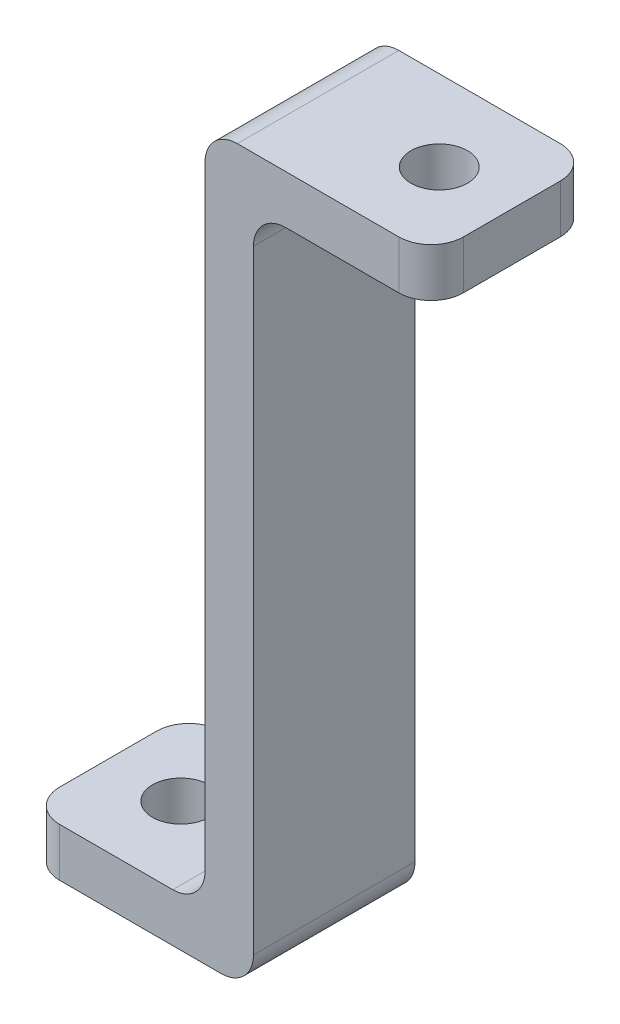
SolidWorks part; units mm, degrees
ref_plane "Front Plane" through (0, 0, 0) normal (0, 0, 1) x (1, 0, 0)
ref_plane "Top Plane" through (0, 0, 0) normal (0, 1, 0) x (1, 0, 0)
ref_plane "Right Plane" through (0, 0, 0) normal (1, 0, 0) x (0, 0, -1)
sketch "Sketch1" plane through (0, 0, 0) normal (0, 0, 1) x (1, 0, 0)
  line L0 (0, 0) -> (14, 0)
  line L1 (14, 0) -> (14, 42)
  line L2 (14, 42) -> (25, 42)
  line L3 (25, 42) -> (25, 45)
  line L4 (25, 45) -> (11, 45)
  line L5 (11, 45) -> (11, 3)
  line L6 (11, 3) -> (0, 3)
  line L7 (0, 3) -> (0, 0)
  dimension "D1" = 3
  dimension "D2" = 3
  dimension "D3" = 11
  dimension "D4" = 3
  dimension "D5" = 11
  dimension "D6" = 42
extrude "Boss-Extrude1" add sketch "Sketch1" against normal blind 10
fillet "Fillet1" radius 2 4 edges at (14, 0, -5) (11, 45, -5) (11, 3, -5) (14, 42, -5)
hole_wizard "Ø3.0mm Dowel Hole1" positions "3DSketch1" profile "Sketch2" hole size "Ø3.0" standard "ANSI Metric" end condition through all
sketch3d "3DSketch1"
  line L0 (0, 0, -5) -> (12, 0, -5) construction
  line L1 (0, 0, -10) -> (0, 0, 0) construction
  line L2 (12, 0, -10) -> (12, 0, 0) construction
  line L4 (4.5, 0, -5) -> (4.5, 0, -10) construction
  line L6 (0, 0, -10) -> (12, 0, -10) construction
  point P0 (4.5, 0, -5)
  dimension "D1" = 4.5
sketch "Sketch2" plane through (4.5, 0, -5) normal (1, 0, 0) x (0, 0, -1)
  line L0 (0, 0) -> (0, 45)
  line L1 (0, 45) -> (1.75, 45)
  line L2 (1.75, 45) -> (1.75, 0)
  line L5 (1.75, 0) -> (0, 0)
  line L11 (0, -6.35) -> (0, 107.95) construction
  dimension "Thru Hole Dia." = 3.5
  dimension "Thru Hole Depth" = 45
hole_wizard "Ø3.0mm Dowel Hole2" positions "Sketch3" profile "Sketch4" hole size "Ø3.0" standard "ANSI Metric" end condition through all
sketch "Sketch3" plane through (0, 45, 0) normal (0, 1, 0) x (1, 0, 0)
  line L0 (25, 5) -> (13, 5) construction
  line L1 (25, 10) -> (25, 0) construction
  line L2 (13, 10) -> (13, 0) construction
  line L4 (20.5, 5) -> (20.5, 10) construction
  line L5 (25, 10) -> (13, 10) construction
  point P0 (20.5, 5)
  dimension "D1" = 4.5
sketch "Sketch4" plane through (20.5, 45, -5) normal (1, 0, 0) x (0, 0, 1)
  line L0 (0, 0) -> (0, 45)
  line L1 (0, 45) -> (1.75, 45)
  line L2 (1.75, 45) -> (1.75, 0)
  line L5 (1.75, 0) -> (0, 0)
  line L11 (0, -6.35) -> (0, 107.95) construction
  dimension "Thru Hole Dia." = 3.5
  dimension "Thru Hole Depth" = 45
fillet "Fillet2" radius 2 4 edges at (25, 43.5, 0) (25, 43.5, -10) (0, 1.5, -10) (0, 1.5, 0)
